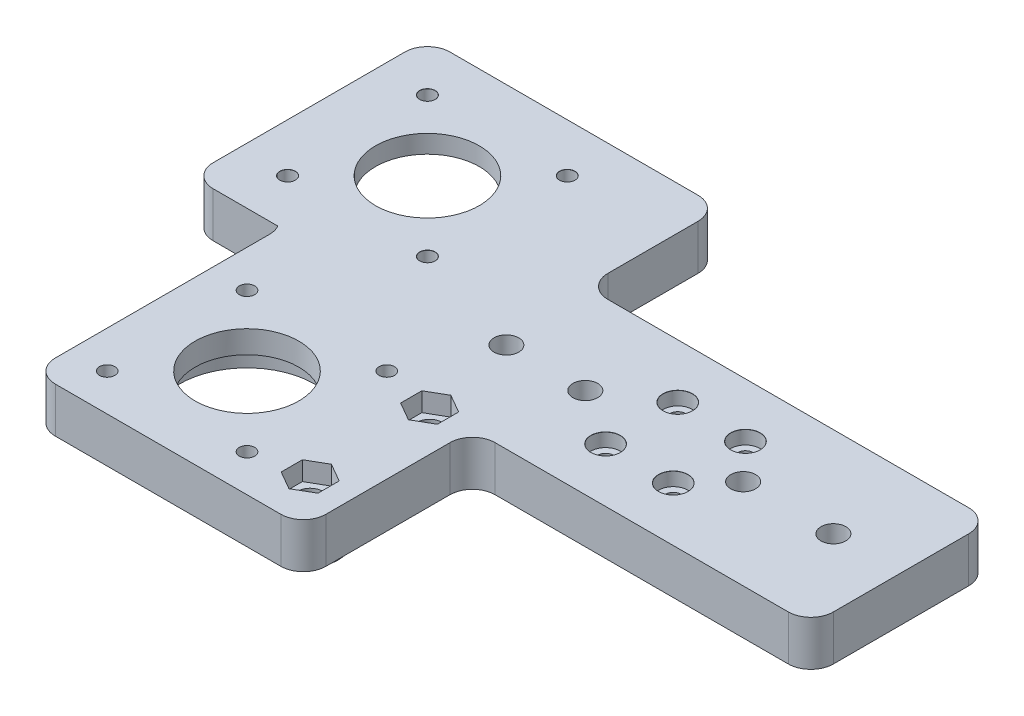
SolidWorks part; units mm, degrees
ref_plane "Front Plane" through (0, 0, 0) normal (0, 0, 1) x (1, 0, 0)
ref_plane "Top Plane" through (0, 0, 0) normal (0, 1, 0) x (1, 0, 0)
ref_plane "Right Plane" through (0, 0, 0) normal (1, 0, 0) x (0, 0, -1)
sketch "Sketch1" plane through (0, 0, 0) normal (0, 1, 0) x (1, 0, 0)
  line L0 (0, 0) -> (110, 0) construction
  line L1 (110, 0) -> (110, 20) construction
  line L2 (110, 20) -> (0, 20) construction
  line L3 (0, 20) -> (0, 0) construction
  line L4 (110, 30) -> (110, -10) construction
  line L5 (110, 30) -> (80, 30) construction
  line L6 (80, 30) -> (80, -10) construction
  line L7 (80, -10) -> (110, -10) construction
  line L8 (0, 67.5) -> (0, -47.5)
  line L16 (0, 67.5) -> (60, 67.5)
  line L18 (0, -47.5) -> (60, -47.5)
  line L19 (60, 67.5) -> (60, 30)
  line L22 (110, -10) -> (60, -10)
  line L23 (60, -10) -> (60, -47.5)
  line L24 (60, 30) -> (110, 30)
  line L25 (110, 30) -> (110, -10)
  point P8 (110, 10)
  point P13 (0, 10)
  dimension "D1" = 20
  dimension "D2" = 37.5
  dimension "D3" = 30
  dimension "D4" = 40
  dimension "D5" = 110
  dimension "D6" = 20
extrude "Boss-Extrude1" add sketch "Sketch1" along normal blind 10
fillet "Fillet1" radius 5 7 edges at (60, 5, -30) (110, 5, -30) (110, 5, 10) (0, 5, 47.5) (0, 5, -67.5) (60, 5, -67.5) (60, 5, 47.5)
sketch "Sketch3" plane through (0, 10, 0) normal (0, 1, 0) x (1, 0, 0)
  line L0 (5, -47.5) -> (55, -47.5) construction
  line L1 (0, 62.5) -> (0, -42.5) construction
  circle A0 centre (23.75, -23.75) radius 11.5
  dimension "D3" = 23
  dimension "D1" = 23.75
  dimension "D2" = 23.75
extrude "Cut-Extrude1" cut sketch "Sketch3" against normal blind 10
sketch "Sketch4" plane through (0, 0, 0) normal (0, -1, 0) x (1, 0, 0)
  line L1 (39.25, 39.25) -> (8.25, 39.25)
  line L2 (39.25, 39.25) -> (39.25, 8.25)
  line L3 (39.25, 8.25) -> (8.25, 8.25)
  line L4 (8.25, 39.25) -> (8.25, 8.25)
  line L5 (39.25, 39.25) -> (8.25, 8.25) construction
  line L6 (39.25, 8.25) -> (8.25, 39.25) construction
  point P0 (23.75, 23.75)
  dimension "D1" = 31
hole_wizard "CBORE for M3 SHCS1" positions "Sketch5" profile "Sketch6" counterbore size "M3" standard "ANSI Metric" end condition through all
sketch "Sketch5" plane through (0, 0, 0) normal (0, -1, 0) x (-1, 0, 0)
  point P0 (-39.25, -8.25)
  point P3 (-8.25, -39.25)
  point P6 (-8.25, -8.25)
  point P9 (-39.25, -39.25)
sketch "Sketch6" plane through (39.25, 0, 8.25) normal (1, 0, 0) x (0, 0, -1)
  line L0 (0, 0) -> (0, 10)
  line L1 (0, 10) -> (1.7, 10)
  line L3 (1.7, 10) -> (1.7, 3)
  line L4 (3.25, 3) -> (1.7, 3)
  line L5 (3.25, 3) -> (3.25, 0.025)
  line L6 (3.25, 0.025) -> (3.275, 0)
  line L7 (3.275, 0) -> (0, 0)
  line L8 (-3.25, 0.025) -> (-3.275, 0) construction
  line L11 (0, -6.35) -> (0, 107.95) construction
  dimension "Thru Hole Dia." = 3.4
  dimension "Thru Hole Depth" = 10
  dimension "C'Bore Dia." = 6.5
  dimension "C'Bore Depth" = 3
  dimension "Near C'Sink Dia." = 6.55
  dimension "Near C'Sink Angle" = 90
sketch "Sketch7" plane through (0, 10, 0) normal (0, 1, 0) x (1, 0, 0)
  line L1 (92.5, 18) -> (77.5, 18)
  line L2 (92.5, 18) -> (92.5, 2)
  line L3 (92.5, 2) -> (77.5, 2)
  line L4 (77.5, 18) -> (77.5, 2)
  line L5 (92.5, 18) -> (77.5, 2) construction
  line L6 (92.5, 2) -> (77.5, 18) construction
  line L7 (110, 10) -> (0, 10)
  line L8 (0, 67.5) -> (0, -47.5) construction
  line L10 (110, 30) -> (110, -10) construction
  point P0 (85, 10)
  dimension "D1" = 15
  dimension "D2" = 16
  dimension "D3" = 25
hole_wizard "CBORE for M3 SHCS2" positions "Sketch8" profile "Sketch9" counterbore size "M3" standard "ANSI Metric" end condition through all
sketch "Sketch8" plane through (0, 10, 0) normal (0, 1, 0) x (1, 0, 0)
  point P0 (77.5, 18)
  point P3 (92.5, 18)
  point P6 (92.5, 2)
  point P9 (77.5, 2)
sketch "Sketch9" plane through (77.5, 10, -18) normal (1, 0, 0) x (0, 0, 1)
  line L0 (0, 0) -> (0, 10)
  line L1 (0, 10) -> (1.7, 10)
  line L3 (1.7, 10) -> (1.7, 3)
  line L4 (3.25, 3) -> (1.7, 3)
  line L5 (3.25, 3) -> (3.25, 0.025)
  line L6 (3.25, 0.025) -> (3.275, 0)
  line L7 (3.275, 0) -> (0, 0)
  line L8 (-3.25, 0.025) -> (-3.275, 0) construction
  line L11 (0, -6.35) -> (0, 107.95) construction
  dimension "Thru Hole Dia." = 3.4
  dimension "Thru Hole Depth" = 10
  dimension "C'Bore Dia." = 6.5
  dimension "C'Bore Depth" = 3
  dimension "Near C'Sink Dia." = 6.55
  dimension "Near C'Sink Angle" = 90
sketch "Sketch10" plane through (0, 0, 0) normal (0, -1, 0) x (1, 0, 0)
  line L0 (110, -10) -> (0, -10) construction
  line L1 (110, 5) -> (110, -25) construction
  line L2 (0, -62.5) -> (0, 42.5) construction
  point P6 (100, -10)
  point P7 (30, -10)
  point P8 (47.5, -10)
  point P9 (65, -10)
  dimension "D1" = 30
  dimension "D2" = 17.5
  dimension "D3" = 17.5
  dimension "D4" = 10
hole_wizard "CBORE for M5 SHCS1" positions "Sketch13" profile "Sketch12" counterbore size "M5" standard "ANSI Metric" end condition through all
sketch "Sketch13" plane through (0, 0, 0) normal (0, -1, 0) x (-1, 0, 0)
  point P0 (-100, 10)
  point P3 (-65, 10)
  point P6 (-47.5, 10)
sketch "Sketch12" plane through (100, 0, -10) normal (1, 0, 0) x (0, 0, -1)
  line L0 (0, 0) -> (0, 10)
  line L1 (0, 10) -> (2.75, 10)
  line L3 (2.75, 10) -> (2.75, 5)
  line L4 (5, 5) -> (2.75, 5)
  line L5 (5, 5) -> (5, 0.025)
  line L6 (5, 0.025) -> (5.025, 0)
  line L7 (5.025, 0) -> (0, 0)
  line L8 (-5, 0.025) -> (-5.025, 0) construction
  line L11 (0, -6.35) -> (0, 107.95) construction
  dimension "Thru Hole Dia." = 5.5
  dimension "Thru Hole Depth" = 10
  dimension "C'Bore Dia." = 10
  dimension "C'Bore Depth" = 5
  dimension "Near C'Sink Dia." = 10.05
  dimension "Near C'Sink Angle" = 90
sketch "Sketch14" plane through (0, 10, 0) normal (0, 1, 0) x (1, 0, 0)
  line L0 (0, 10) -> (-17.5, 10)
  line L1 (0, 62.5) -> (0, -42.5) construction
  line L2 (-17.5, 10) -> (-17.5, 67.5)
  line L3 (-17.5, 67.5) -> (5, 67.5)
  line L4 (0, 62.5) -> (0, 10)
  arc A0 (5, 67.5) -> (0, 62.5) centre (5, 62.5) ccw construction
  arc A1 (5, 67.5) -> (0, 62.5) centre (5, 62.5) ccw
  dimension "D1" = 17.5
extrude "Boss-Extrude2" add sketch "Sketch14" against normal blind 10
sketch "Sketch15" plane through (0, 10, 0) normal (0, 1, 0) x (1, 0, 0)
  line L0 (-17.5, 67.5) -> (55, 67.5)
  line L1 (-17.5, 67.5) -> (-17.5, 57.5)
  line L2 (-17.5, 67.5) -> (-17.5, 10) construction
  line L3 (-17.5, 57.5) -> (60, 57.5)
  line L5 (60, 35) -> (60, 62.5) construction
  line L6 (60, 57.5) -> (60, 62.5)
  arc A2 (60, 62.5) -> (55, 67.5) centre (55, 62.5) ccw construction
  arc A3 (60, 62.5) -> (55, 67.5) centre (55, 62.5) ccw
  dimension "D1" = 10
extrude "Cut-Extrude2" cut sketch "Sketch15" against normal blind 10
fillet "Fillet2" radius 5 4 edges at (0, 5, -10) (60, 5, -57.5) (-17.5, 5, -57.5) (-17.5, 5, -10)
sketch "Sketch16" plane through (0, 10, 0) normal (0, 1, 0) x (1, 0, 0)
  line L0 (-12.5, 57.5) -> (55, 57.5) construction
  line L1 (-17.5, 52.5) -> (-17.5, 15) construction
  circle A0 centre (6.25, 33.75) radius 11.5
  dimension "D1" = 23
  dimension "D2" = 23.75
  dimension "D3" = 23.75
extrude "Cut-Extrude3" cut sketch "Sketch16" against normal through all
sketch "Sketch17" plane through (0, 10, 0) normal (0, 1, 0) x (1, 0, 0)
  line L1 (21.75, 49.25) -> (-9.25, 49.25)
  line L2 (21.75, 49.25) -> (21.75, 18.25)
  line L3 (21.75, 18.25) -> (-9.25, 18.25)
  line L4 (-9.25, 49.25) -> (-9.25, 18.25)
  line L5 (21.75, 49.25) -> (-9.25, 18.25) construction
  line L6 (21.75, 18.25) -> (-9.25, 49.25) construction
  point P0 (6.25, 33.75)
  dimension "D1" = 31
hole_wizard "M3 Clearance Hole1" positions "Sketch18" profile "Sketch19" hole size "M3" standard "ANSI Metric" end condition through all
sketch "Sketch18" plane through (0, 10, 0) normal (0, 1, 0) x (1, 0, 0)
  point P0 (-9.25, 49.25)
  point P3 (21.75, 49.25)
  point P6 (21.75, 18.25)
  point P9 (-9.25, 18.25)
sketch "Sketch19" plane through (-9.25, 10, -49.25) normal (1, 0, 0) x (0, 0, 1)
  line L0 (0, 0) -> (0, 10)
  line L1 (0, 10) -> (1.7, 10)
  line L2 (1.7, 10) -> (1.7, 0.025)
  line L3 (1.7, 0.025) -> (1.725, 0)
  line L5 (1.725, 0) -> (0, 0)
  line L6 (-1.7, 0.025) -> (-1.725, 0) construction
  line L11 (0, -6.35) -> (0, 107.95) construction
  dimension "Thru Hole Dia." = 3.4
  dimension "Thru Hole Depth" = 10
  dimension "Near C'Sink Dia." = 3.45
  dimension "Near C'Sink Angle" = 90
sketch "Sketch20" plane through (0, 10, 0) normal (0, 1, 0) x (1, 0, 0)
  line L0 (23.75, -23.75) -> (60, -23.75) construction
  line L1 (60, -42.5) -> (60, -10) construction
  line L2 (51, -10.51) -> (51, -36.99) construction
  line L4 (55.075, -8.1573) -> (51, -5.8046)
  line L5 (51, -5.8046) -> (46.925, -8.1573)
  line L6 (46.925, -8.1573) -> (46.925, -12.8627)
  line L7 (46.925, -12.8627) -> (51, -15.2154)
  line L8 (51, -15.2154) -> (55.075, -12.8627)
  line L9 (55.075, -12.8627) -> (55.075, -8.1573)
  line L10 (51, -32.2846) -> (46.925, -34.6373)
  line L11 (46.925, -34.6373) -> (46.925, -39.3427)
  line L12 (46.925, -39.3427) -> (51, -41.6954)
  line L13 (51, -41.6954) -> (55.075, -39.3427)
  line L14 (55.075, -39.3427) -> (55.075, -34.6373)
  line L15 (55.075, -34.6373) -> (51, -32.2846)
  line L18 (0, 5) -> (0, -42.5) construction
  circle A0 centre (51, -10.51) radius 4.075 construction
  circle A1 centre (51, -36.99) radius 4.075 construction
  point P8 (51, -23.75)
  point P25 (51, -36.99)
  point P26 (51, -10.51)
  dimension "D1" = 26.48
  dimension "D2" = 9
  dimension "D3" = 8.15
extrude "Cut-Extrude4" cut sketch "Sketch20" against normal blind 4.2
hole_wizard "M5 Clearance Hole1" positions "Sketch22" profile "Sketch23" hole size "M5" standard "ANSI Metric" end condition through all
sketch "Sketch22" plane through (0, 10, 0) normal (0, 1, 0) x (1, 0, 0)
  point P0 (51, -10.51)
  point P3 (51, -36.99)
sketch "Sketch23" plane through (51, 10, 10.51) normal (1, 0, 0) x (0, 0, 1)
  line L0 (0, 0) -> (0, 10)
  line L1 (0, 10) -> (2.75, 10)
  line L2 (2.75, 10) -> (2.75, 0.025)
  line L3 (2.75, 0.025) -> (2.775, 0)
  line L5 (2.775, 0) -> (0, 0)
  line L6 (-2.75, 0.025) -> (-2.775, 0) construction
  line L11 (0, -6.35) -> (0, 107.95) construction
  dimension "Thru Hole Dia." = 5.5
  dimension "Thru Hole Depth" = 10
  dimension "Near C'Sink Dia." = 5.55
  dimension "Near C'Sink Angle" = 90
sketch "Sketch25" plane through (0, 0, 0) normal (0, -1, 0) x (1, 0, 0)
  circle A0 centre (23.75, 23.75) radius 15
  dimension "D1" = 30
extrude "Cut-Extrude6" cut sketch "Sketch25" against normal blind 5
sketch "Sketch26" plane through (0, 0, 0) normal (0, -1, 0) x (1, 0, 0)
  circle A0 centre (51, 36.99) radius 6.25
  circle A1 centre (51, 36.99) radius 2.75 construction
  circle A2 centre (51, 36.99) radius 2.75
  circle A3 centre (51, 10.51) radius 6.25
  circle A4 centre (51, 10.51) radius 2.75 construction
  circle A5 centre (51, 10.51) radius 2.75
  dimension "D1" = 12.5
extrude "Boss-Extrude3" add sketch "Sketch26" along normal blind 2.9
sketch "Sketch27" plane through (0, 10, 0) normal (0, 1, 0) x (1, 0, 0)
  line L0 (65, 30) -> (45, 30)
  line L1 (45, 30) -> (45, 57.5)
  line L2 (-12.5, 57.5) -> (55, 57.5) construction
  line L3 (45, 57.5) -> (55, 57.5)
  line L4 (60, 35) -> (60, 52.5) construction
  line L5 (60, 35) -> (60, 52.5)
  arc A0 (60, 35) -> (65, 30) centre (65, 35) ccw construction
  arc A1 (60, 52.5) -> (55, 57.5) centre (55, 52.5) ccw construction
  arc A2 (60, 35) -> (65, 30) centre (65, 35) ccw
  arc A3 (60, 52.5) -> (55, 57.5) centre (55, 52.5) ccw
  dimension "D1" = 15
extrude "Cut-Extrude7" cut sketch "Sketch27" against normal blind 10
fillet "Fillet3" radius 5 3 edges at (45, 5, -57.5) (45, 5, -30) (60, 5, 10)
sketch "Sketch31" plane through (0, 10, 0) normal (0, 1, 0) x (1, 0, 0)
  line L0 (-10.5429, 54.2071) -> (-14.2071, 50.5429) construction
  line L1 (22.3358, 54.5) -> (-9.8358, 54.5) construction
  line L2 (26.7071, 50.5429) -> (23.0429, 54.2071) construction
  line L3 (27, 17.6642) -> (27, 49.8358) construction
  line L4 (23.0429, 13.2929) -> (26.7071, 16.9571) construction
  line L5 (-9.8358, 13) -> (22.3358, 13) construction
  line L6 (-14.2071, 16.9571) -> (-10.5429, 13.2929) construction
  line L7 (-14.5, 49.8358) -> (-14.5, 17.6642) construction
  line L8 (-10.5429, 54.2071) -> (-14.2071, 50.5429) construction
  line L9 (22.3358, 54.5) -> (-9.8358, 54.5) construction
  line L10 (-15.5, 49.8358) -> (-15.5, 17.6642)
  line L11 (-14.9142, 16.25) -> (-11.25, 12.5858)
  line L12 (-9.8358, 12) -> (22.3358, 12)
  line L13 (23.75, 12.5858) -> (27.4142, 16.25)
  line L14 (28, 17.6642) -> (28, 49.8358)
  line L15 (27.4142, 51.25) -> (23.75, 54.9142)
  line L16 (22.3358, 55.5) -> (-9.8358, 55.5)
  line L17 (-11.25, 54.9142) -> (-14.9142, 51.25)
  line L30 (26.7071, 50.5429) -> (23.0429, 54.2071) construction
  line L31 (27, 17.6642) -> (27, 49.8358) construction
  line L32 (23.0429, 13.2929) -> (26.7071, 16.9571) construction
  line L33 (-9.8358, 13) -> (22.3358, 13) construction
  line L34 (-14.2071, 16.9571) -> (-10.5429, 13.2929) construction
  line L35 (-14.5, 49.8358) -> (-14.5, 17.6642) construction
  arc A0 (-14.2071, 50.5429) -> (-14.5, 49.8358) centre (-13.5, 49.8358) ccw construction
  arc A1 (-9.8358, 54.5) -> (-10.5429, 54.2071) centre (-9.8358, 53.5) ccw construction
  arc A2 (23.0429, 54.2071) -> (22.3358, 54.5) centre (22.3358, 53.5) ccw construction
  arc A3 (27, 49.8358) -> (26.7071, 50.5429) centre (26, 49.8358) ccw construction
  arc A4 (26.7071, 16.9571) -> (27, 17.6642) centre (26, 17.6642) ccw construction
  arc A5 (22.3358, 13) -> (23.0429, 13.2929) centre (22.3358, 14) ccw construction
  arc A6 (-10.5429, 13.2929) -> (-9.8358, 13) centre (-9.8358, 14) ccw construction
  arc A7 (-14.5, 17.6642) -> (-14.2071, 16.9571) centre (-13.5, 17.6642) ccw construction
  arc A8 (-14.2071, 50.5429) -> (-14.5, 49.8358) centre (-13.5, 49.8358) ccw construction
  arc A9 (-14.9142, 51.25) -> (-15.5, 49.8358) centre (-13.5, 49.8358) ccw
  arc A10 (-15.5, 17.6642) -> (-14.9142, 16.25) centre (-13.5, 17.6642) ccw
  arc A11 (-11.25, 12.5858) -> (-9.8358, 12) centre (-9.8358, 14) ccw
  arc A12 (22.3358, 12) -> (23.75, 12.5858) centre (22.3358, 14) ccw
  arc A14 (27.4142, 16.25) -> (28, 17.6642) centre (26, 17.6642) ccw
  arc A15 (28, 49.8358) -> (27.4142, 51.25) centre (26, 49.8358) ccw
  arc A17 (23.75, 54.9142) -> (22.3358, 55.5) centre (22.3358, 53.5) ccw
  arc A27 (-9.8358, 54.5) -> (-10.5429, 54.2071) centre (-9.8358, 53.5) ccw construction
  arc A28 (23.0429, 54.2071) -> (22.3358, 54.5) centre (22.3358, 53.5) ccw construction
  arc A29 (27, 49.8358) -> (26.7071, 50.5429) centre (26, 49.8358) ccw construction
  arc A30 (26.7071, 16.9571) -> (27, 17.6642) centre (26, 17.6642) ccw construction
  arc A31 (22.3358, 13) -> (23.0429, 13.2929) centre (22.3358, 14) ccw construction
  arc A32 (-10.5429, 13.2929) -> (-9.8358, 13) centre (-9.8358, 14) ccw construction
  arc A33 (-14.5, 17.6642) -> (-14.2071, 16.9571) centre (-13.5, 17.6642) ccw construction
  arc A34 (-9.8358, 55.5) -> (-11.25, 54.9142) centre (-9.8358, 53.5) ccw
  dimension "D1" = 1
extrude "Cut-Extrude9" cut sketch "Sketch31" along normal blind 6 from surface starting at face at (51, 0, 43.24)
sketch "Sketch32" plane through (0, 0, 0) normal (0, -1, 0) x (1, 0, 0)
  line L1 (-20, -7.5) -> (-20, -60)
  line L2 (45, -52.5) -> (45, -60)
  line L3 (45, -60) -> (-20, -60)
  line L4 (-12.5, -57.5) -> (40, -57.5) construction
  line L5 (-17.5, -52.5) -> (-17.5, -15) construction
  line L6 (-12.5, -57.5) -> (40, -57.5)
  line L7 (-17.5, -52.5) -> (-17.5, -15)
  line L8 (-0.6699, -7.5) -> (-20, -7.5)
  line L10 (-12.5, -10) -> (-5, -10) construction
  line L11 (-12.5, -10) -> (-5, -10)
  arc A0 (40, -57.5) -> (45, -52.5) centre (40, -52.5) ccw construction
  arc A1 (-17.5, -52.5) -> (-12.5, -57.5) centre (-12.5, -52.5) ccw construction
  arc A2 (-12.5, -10) -> (-17.5, -15) centre (-12.5, -15) ccw construction
  arc A3 (40, -57.5) -> (45, -52.5) centre (40, -52.5) ccw
  arc A4 (-17.5, -52.5) -> (-12.5, -57.5) centre (-12.5, -52.5) ccw
  arc A5 (-12.5, -10) -> (-17.5, -15) centre (-12.5, -15) ccw
  arc A7 (-5, -10) -> (0, -5) centre (-5, -5) ccw construction
  arc A8 (-5, -10) -> (-0.6699, -7.5) centre (-5, -5) ccw
  dimension "D1" = 7.5
  dimension "D2" = 7.5
  dimension "D3" = 7.5
extrude "Boss-Extrude5" add sketch "Sketch32" against normal up to surface (10 mm away) up to face at (39.5, 10, -8)
fillet "Fillet4" radius 5 3 edges at (45, 5, -60) (-20, 5, -60) (-20, 5, -7.5)
sketch "Sketch33" plane through (0, 0, 0) normal (0, -1, 0) x (1, 0, 0)
  line L0 (105, -30) -> (135, -30)
  line L1 (105, 10) -> (135, 10)
  line L2 (135, 10) -> (135, -30)
  line L3 (110, 5) -> (110, -25) construction
  line L4 (110, 5) -> (110, -25)
  arc A0 (110, 5) -> (105, 10) centre (105, 5) ccw construction
  arc A1 (105, -30) -> (110, -25) centre (105, -25) ccw construction
  arc A2 (110, 5) -> (105, 10) centre (105, 5) ccw
  arc A3 (105, -30) -> (110, -25) centre (105, -25) ccw
  dimension "D1" = 25
extrude "Boss-Extrude6" add sketch "Sketch33" against normal up to surface (10 mm away) up to face at (39.173, 10, -8.0754)
sketch "Sketch34" plane through (0, 0, 0) normal (0, -1, 0) x (1, 0, 0)
  line L0 (135, -30) -> (135, 10) construction
  line L1 (135, -10) -> (-19.3472, -10.0297) construction
  arc A1 (-15, -7.5) -> (-20, -12.5) centre (-15, -12.5) ccw construction
  circle A2 centre (100, -10) radius 2.75 construction
  point P0 (120, -10.0029)
  dimension "D1" = 20
hole_wizard "CBORE for M5 SHCS2" positions "Sketch35" profile "Sketch36" counterbore size "M5" standard "ANSI Metric" end condition through all
sketch "Sketch35" plane through (0, 0, 0) normal (0, -1, 0) x (-1, 0, 0)
  point P0 (-120, 10.0029)
sketch "Sketch36" plane through (120, 0, -10.0029) normal (1, 0, 0) x (0, 0, -1)
  line L0 (0, 0) -> (0, 10)
  line L1 (0, 10) -> (2.75, 10)
  line L3 (2.75, 10) -> (2.75, 5)
  line L4 (5, 5) -> (2.75, 5)
  line L5 (5, 5) -> (5, 0.021)
  line L6 (5, 0.021) -> (5.025, 0)
  line L7 (5.025, 0) -> (0, 0)
  line L8 (-5, 0.021) -> (-5.025, 0) construction
  line L11 (0, -6.35) -> (0, 107.95) construction
  dimension "Thru Hole Dia." = 5.5
  dimension "Thru Hole Depth" = 10
  dimension "C'Bore Dia." = 10
  dimension "C'Bore Depth" = 5
  dimension "Near C'Sink Dia." = 10.05
  dimension "Near C'Sink Angle" = 100
fillet "Fillet5" radius 5 2 edges at (135, 5, -30) (135, 5, 10)
